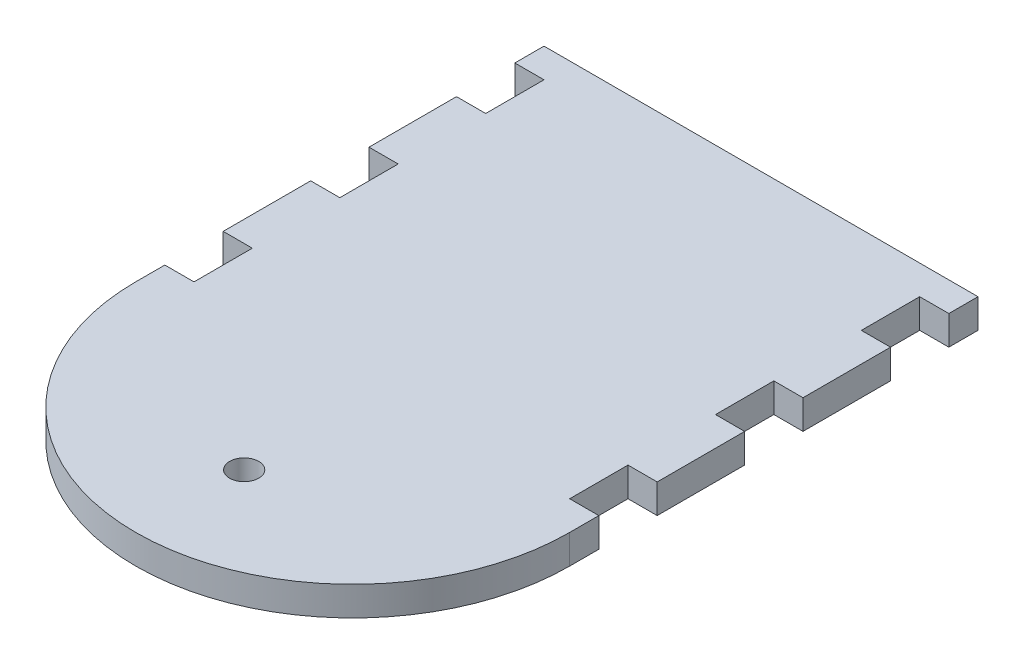
SolidWorks part; units mm, degrees
ref_plane "Front Plane" through (0, 0, 0) normal (0, 0, 1) x (1, 0, 0)
ref_plane "Top Plane" through (0, 0, 0) normal (0, 1, 0) x (1, 0, 0)
ref_plane "Right Plane" through (0, 0, 0) normal (1, 0, 0) x (0, 0, -1)
sketch "Sketch1" plane through (0, 0, 0) normal (0, 1, 0) x (1, 0, 0)
  line L0 (-47.244, 0) -> (47.244, 0) construction
  line L1 (-47.244, 44.45) -> (47.244, 44.45) construction
  line L2 (-47.244, 44.45) -> (-47.244, -44.45) construction
  line L3 (-47.244, -44.45) -> (47.244, -44.45) construction
  line L4 (47.244, 44.45) -> (47.244, -44.45) construction
  line L5 (-47.244, 44.45) -> (47.244, -44.45) construction
  line L6 (-47.244, -44.45) -> (47.244, 44.45) construction
  line L7 (-47.244, 44.45) -> (47.244, 44.45)
  line L8 (47.244, 44.45) -> (47.244, 38.1)
  line L9 (47.244, 38.1) -> (40.894, 38.1)
  line L10 (40.894, 38.1) -> (40.894, 25.4)
  line L11 (40.894, 25.4) -> (47.244, 25.4)
  line L12 (47.244, 25.4) -> (47.244, 6.35)
  line L13 (47.244, 6.35) -> (40.894, 6.35)
  line L14 (40.894, 6.35) -> (40.894, -6.35)
  line L15 (40.894, -6.35) -> (47.244, -6.35)
  line L16 (47.244, -6.35) -> (47.244, -25.4)
  line L17 (47.244, -25.4) -> (40.894, -25.4)
  line L18 (40.894, -25.4) -> (40.894, -38.1)
  line L19 (40.894, -38.1) -> (47.244, -38.1)
  line L20 (47.244, -38.1) -> (47.244, -44.45)
  line L21 (0, 44.45) -> (0, -44.45) construction
  line L22 (-40.894, -38.1) -> (-47.244, -38.1)
  line L23 (-40.894, -25.4) -> (-40.894, -38.1)
  line L24 (-47.244, -25.4) -> (-40.894, -25.4)
  line L25 (-40.894, -6.35) -> (-47.244, -6.35)
  line L26 (-40.894, 6.35) -> (-40.894, -6.35)
  line L27 (-47.244, 6.35) -> (-40.894, 6.35)
  line L28 (-40.894, 25.4) -> (-47.244, 25.4)
  line L29 (-40.894, 38.1) -> (-40.894, 25.4)
  line L30 (-47.244, 38.1) -> (-40.894, 38.1)
  line L31 (-47.244, 44.45) -> (-47.244, -44.45) construction
  line L32 (-47.244, -38.1) -> (-47.244, -44.45)
  line L33 (-47.244, -6.35) -> (-47.244, -25.4)
  line L34 (-47.244, 25.4) -> (-47.244, 6.35)
  line L35 (-47.244, 44.45) -> (-47.244, 38.1)
  line L36 (0, -44.45) -> (0, -91.694) construction
  arc A0 (-47.244, -44.45) -> (47.244, -44.45) centre (0, -44.45) ccw
  circle A1 centre (0, -68.072) radius 3.175
  point P0 (0, 0)
  point P9 (0, 0)
  dimension "D6" = 6.35
  dimension "D1" = 94.488
  dimension "D2" = 88.9
  dimension "D3" = 76.2
  dimension "D4" = 19.05
  dimension "D5" = 6.35
  dimension "D7" = 6.35
  dimension "D8" = 6.35
  dimension "D9" = 6.35
extrude "Boss-Extrude1" add sketch "Sketch1" along normal blind 6.35
